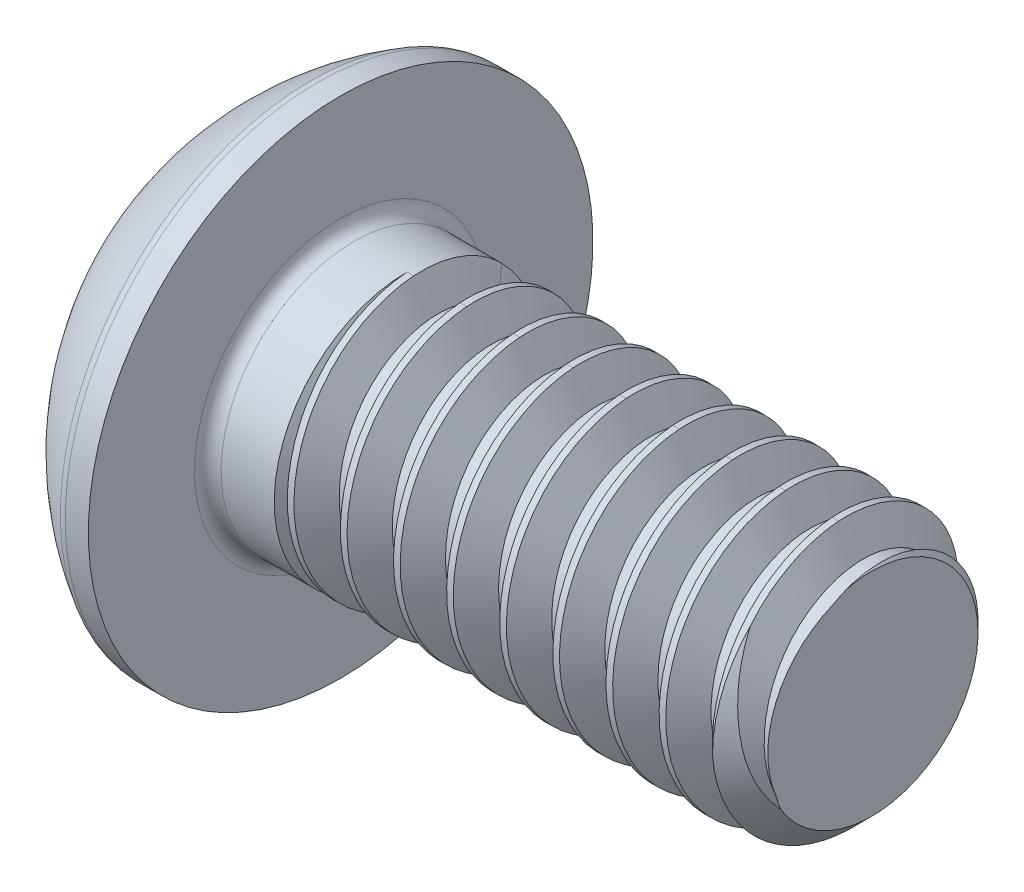
SolidWorks part; units mm, degrees
ref_plane "Alzado" through (0, 0, 0) normal (0, 0, 1) x (1, 0, 0)
ref_plane "Planta" through (0, 0, 0) normal (0, 1, 0) x (1, 0, 0)
ref_plane "Vista lateral" through (0, 0, 0) normal (1, 0, 0) x (0, 0, -1)
sketch "Croquis1" plane through (0, 0, 0) normal (0, 0, 1) x (1, 0, 0)
  line L0 (0, 0) -> (-5.4828, 0) construction
  line L1 (0, 0) -> (0, 0.8)
  line L2 (0, 0.8) -> (-0.2, 1)
  line L3 (-3.9, 1) -> (-0.2, 1)
  line L4 (-4, 1.1) -> (-4, 1.9)
  line L5 (-4, 1.9) -> (-4.2, 1.9)
  line L6 (-5.1, 0.95) -> (-5.1, 0)
  line L7 (-5.1, 0) -> (0, 0)
  arc A0 (-4, 1.1) -> (-3.9, 1) centre (-3.9, 1.1) ccw
  arc A1 (-4.2, 1.9) -> (-5.1, 0.95) centre (-3.1556, 0.0093) ccw
  dimension "D6" = 0.1
  dimension "D9" = 2.16
  dimension "D1" = 5.1
  dimension "D2" = 1.9
  dimension "D3" = 3.8
  dimension "D4" = 2
  dimension "D5" = 1.1
  dimension "D7" = 0.2
  dimension "D8" = 45
  dimension "D10" = 0.2
revolve "Revolución1" add sketch "Croquis1" angle 360 about L0
hole_wizard "Diámetro de taladro Ø1.25 (1.25)1" positions "Croquis3D1" profile "Croquis2" hole size "Ø1.25" standard "ISO"
sketch3d "Croquis3D1"
  line L0 (-5.7398, 0, 0) -> (-2.4705, 0, 0) construction
  point P0 (-5.1, 0, 0)
sketch "Croquis2" plane through (-5.1, 0, 0) normal (0, 1, 0) x (0, 0, 1)
  line L0 (0, 0) -> (0, 1.0255)
  line L1 (0, 1.0255) -> (0.625, 0.65)
  line L2 (0.625, 0.65) -> (0.625, 0)
  line L5 (0.625, 0) -> (0, 0)
  line L10 (0, 1.0255) -> (-0.625, 0.65) construction
  line L11 (0, -6.35) -> (0, 107.95) construction
  dimension "Diámetro de taladro" = 1.25
  dimension "Profundidad de taladro" = 0.65
  dimension "Ángulo de perforador" = 118
sketch "Croquis3" plane through (-5.1, 0, 0) normal (-1, 0, 0) x (0, 0, 1)
  line L1 (-0.7217, 0) -> (-0.3608, -0.625)
  line L2 (-0.3608, -0.625) -> (0.3608, -0.625)
  line L3 (0.3608, -0.625) -> (0.7217, 0)
  line L4 (0.7217, 0) -> (0.3608, 0.625)
  line L5 (0.3608, 0.625) -> (-0.3608, 0.625)
  line L6 (-0.3608, 0.625) -> (-0.7217, 0)
  circle A0 centre (0, 0) radius 0.625 construction
  circle A1 centre (0, 0) radius 0.625 construction
extrude "Cortar-Extruir1" cut sketch "Croquis3" against normal blind 0.65
fillet "Redondeo1" radius 0.1 2 edges at (-4.2, 1.9, 0) (-5.1, 0.95, 0)
fillet "Redondeo2" radius 0.05 12 edges at (-5.1, -0.625, 0) (-5.1, -0.3125, 0.5413) (-5.1, -0.3125, -0.5413) (-5.1, 0.3125, 0.5413) (-5.1, 0.3125, -0.5413) (-5.1, 0.625, 0) (-4.775, 0.625, -0.3608) (-4.775, 0, -0.7217) (-4.775, -0.625, -0.3608) (-4.775, -0.625, 0.3608) (-4.775, 0, 0.7217) (-4.775, 0.625, 0.3608)
thread "Rosca1" pitch 0.4 method cut profile "Perfil de rosca1" start angle 0, offset 1, length 0, pitch 0.4, diameter 2
ref_plane "Plano1" through (1, 0, 1) normal (0, -1, 0) x (0, 0, 1)
sketch "Perfil de rosca1" plane through (1, 0, 1) normal (0, -1, 0) x (0, 0, 1)
  line L0 (0, 0) -> (0, 0.4) construction
  line L11 (0, 0) -> (0, 0.35)
  line L12 (0, 0.35) -> (-0.2165, 0.225)
  line L13 (-0.2165, 0.225) -> (-0.2165, 0.125)
  line L15 (-0.2165, 0.125) -> (0, 0)
  line L17 (-0.2165, 0.175) -> (0, 0.175) construction
  point P2 (0, 0)
  dimension "Pitch" = 0.4
  dimension "Profile_Angle" = 60
  dimension "Profile_Land" = 0.1
  dimension "Profile_Height" = 0.2165
sketch "Croquis8" plane through (0, 0, 0) normal (0, 0, 1) x (1, 0, 0)
  line L0 (0, 0) -> (-5.4828, 0) construction
  line L2 (-4.0251, 0) -> (-4.4115, 1.1)
  line L3 (-3.9, 1) -> (-3.5, 1)
  line L4 (-4, -1.9) -> (-4, 1.9) construction
  line L8 (-3.5, 1) -> (-2.9226, 0)
  line L9 (-4, 1.1) -> (-4.4115, 1.1)
  line L12 (-4.0251, 0) -> (-2.9226, 0)
  arc A0 (-4, 1.1) -> (-3.9, 1) centre (-3.9, 1.1) ccw
  point P10 (0, 0)
  dimension "D3" = 0.1
  dimension "D2" = 0.5
  dimension "D4" = 60
  dimension "D10" = 2
revolve "Revolución2" add sketch "Croquis8" angle 360 about L0
